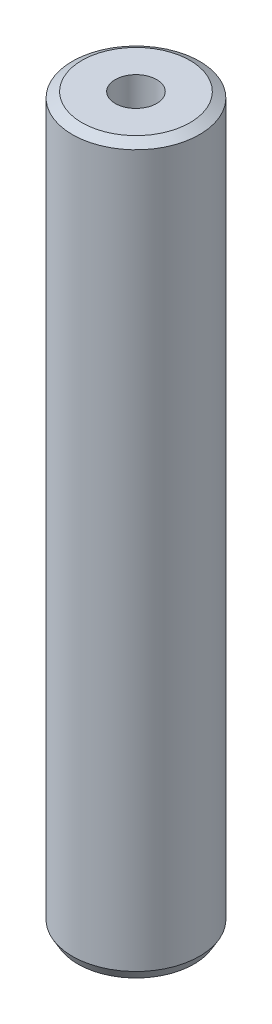
SolidWorks part; units mm, degrees
ref_plane "Front Plane" through (0, 0, 0) normal (0, 0, 1) x (1, 0, 0)
ref_plane "Top Plane" through (0, 0, 0) normal (0, 1, 0) x (1, 0, 0)
ref_plane "Right Plane" through (0, 0, 0) normal (1, 0, 0) x (0, 0, -1)
sketch "Sketch1" plane through (0, 0, 0) normal (0, 1, 0) x (1, 0, 0)
  circle A0 centre (0, 0) radius 52.5
  dimension "SHAFT_OD" = 105
extrude "Boss-Extrude1" add sketch "Sketch1" along normal blind 600
sketch "Sketch2" plane through (0, 0, 0) normal (0, 1, 0) x (1, 0, 0)
  circle A0 centre (0, 0) radius 17.1157
  dimension "BORE_D" = 34.2313
extrude "Cut-Extrude1" cut sketch "Sketch2" along normal through all
chamfer "Chamfer1" distance 4.5576 angle 60 2 edges at (0, 600, 52.5) (0, 0, 52.5) first distance on face at (0, 600, 52.5) first distance on face at (0, 0, 17.1157)
